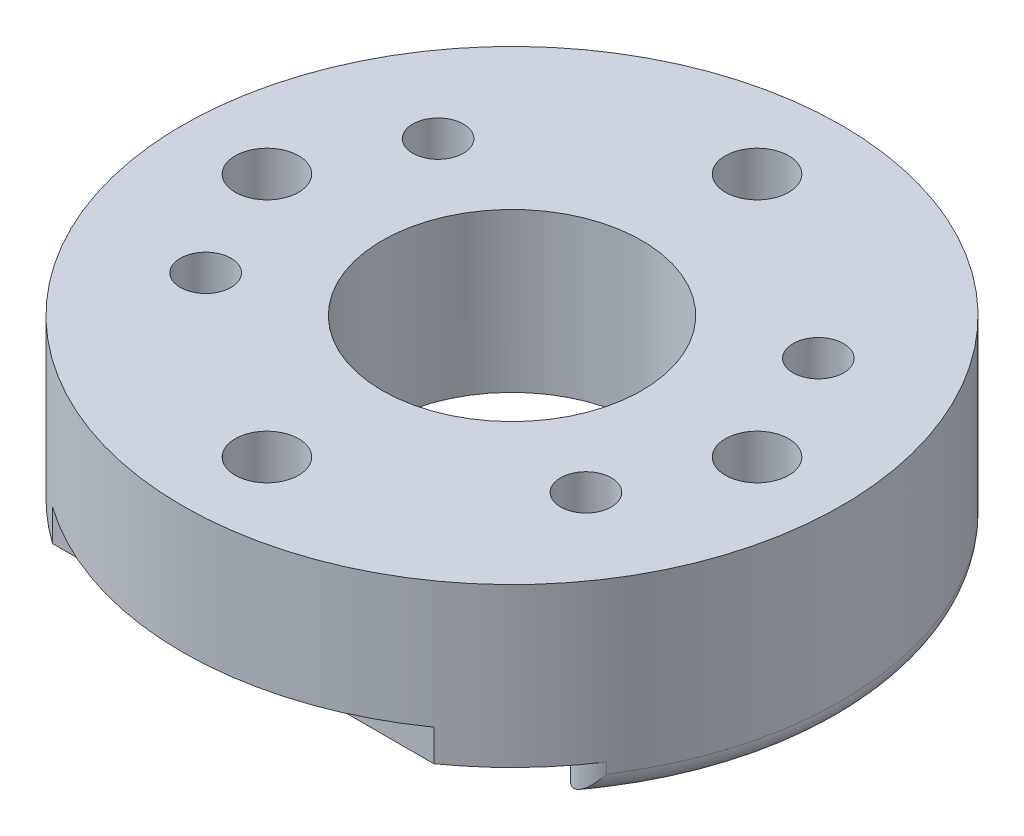
SolidWorks part; units mm, degrees
ref_plane "Front Plane" through (0, 0, 0) normal (0, 0, 1) x (1, 0, 0)
ref_plane "Top Plane" through (0, 0, 0) normal (0, 1, 0) x (1, 0, 0)
ref_plane "Right Plane" through (0, 0, 0) normal (1, 0, 0) x (0, 0, -1)
sketch "Sketch1" plane through (0, 0, 0) normal (0, 1, 0) x (1, 0, 0)
  arc A0 (16.6, 0) -> (-16.6, 0) centre (0, 0) ccw construction
  arc A1 (16.6, 0) -> (-16.6, 0) centre (0, 0) ccw
  circle A2 centre (0, 0) radius 8.5 construction
  circle A3 centre (0, 0) radius 8.5
ref_plane "Plane1" through (0, -7.5, 0) normal (0, 1, 0) x (1, 0, 0)
sketch "Sketch2" plane through (0, -7.5, 0) normal (0, 1, 0) x (1, 0, 0)
  line L4 (-11, 7.5) -> (-11, -20.5)
  line L5 (-11, -20.5) -> (11, -20.5)
  line L6 (11, -20.5) -> (11, 7.5)
  line L7 (11, 7.5) -> (-11, 7.5)
  line L8 (-11, 7.5) -> (-11, -20.5)
  line L9 (-11, -20.5) -> (11, -20.5)
  line L10 (11, -20.5) -> (11, 7.5)
  line L11 (11, 7.5) -> (-11, 7.5)
  line L16 (2.58, 2.15) -> (-2.58, 2.15)
  line L17 (2.58, -2.15) -> (2.58, 2.15)
  line L18 (-2.58, -2.15) -> (2.58, -2.15)
  line L19 (-2.58, 2.15) -> (-2.58, -2.15)
  line L20 (2.58, 2.15) -> (-2.58, 2.15)
  line L21 (2.58, -2.15) -> (2.58, 2.15)
  line L22 (-2.58, -2.15) -> (2.58, -2.15)
  line L23 (-2.58, 2.15) -> (-2.58, -2.15)
  circle A0 centre (9, -5.5) radius 1.3 construction
  circle A1 centre (9, 5.5) radius 1.3 construction
  circle A2 centre (-9, 5.5) radius 1.3 construction
  circle A3 centre (-9, -5.5) radius 1.3 construction
  circle A4 centre (9, -5.5) radius 1.3
  circle A5 centre (9, 5.5) radius 1.3
  circle A6 centre (-9, 5.5) radius 1.3
  circle A7 centre (-9, -5.5) radius 1.3
  dimension "D1" = 0
  dimension "D2" = 0
ref_plane "Plane2" through (0, -5.5, 0) normal (0, -1, 0) x (-1, 0, 0)
sketch "Sketch3" plane through (0, -5.5, 0) normal (0, -1, 0) x (-1, 0, 0)
  circle A0 centre (0, 0) radius 5.15 construction
  circle A1 centre (0, 0) radius 5.15
sketch "Sketch4" plane through (0, 0, 0) normal (0, 1, 0) x (1, 0, 0)
  circle A0 centre (0, 0) radius 15.6
  arc A1 (16.6, 0) -> (-16.6, 0) centre (0, 0) ccw construction
  circle A2 centre (0, 0) radius 5.15 construction
  circle A3 centre (0, 0) radius 5.15 construction
  circle A4 centre (0, 0) radius 6.15
  dimension "D1" = 1
  dimension "D2" = 1
extrude "Boss-Extrude1" add sketch "Sketch4" against normal up to surface (7.5 mm away) up to plane "Plane1"
sketch "Sketch5" plane through (0, -7.5, 0) normal (0, -1, 0) x (1, 0, 0)
  line L0 (11, 20.5) -> (11, -7.5) construction
  line L1 (11, -7.5) -> (-11, -7.5) construction
  line L2 (-11, -7.5) -> (-11, 20.5) construction
  line L3 (11, 11.0616) -> (11, -7.5) construction
  line L4 (11, -7.5) -> (-11, -7.5) construction
  line L5 (-11, -7.5) -> (-11, 11.0616) construction
  line L6 (11.2, 10.8591) -> (11.2, -7.7)
  line L7 (11.2, -7.7) -> (-11.2, -7.7)
  line L8 (-11.2, -7.7) -> (-11.2, 10.8591)
  line L9 (-11.2, -7.7) -> (-11.2, 20.5) construction
  line L10 (-11, -7.5) -> (-11, 20.5) construction
  line L11 (11, 20.5) -> (11, -7.5) construction
  line L12 (11.2, 20.5) -> (11.2, -7.7) construction
  arc A0 (-11.2, 10.8591) -> (11.2, 10.8591) centre (0, 0) ccw
  dimension "D1" = 0.2
extrude "Boss-Extrude2" add sketch "Sketch5" along normal blind 1.5
sketch "Sketch6" plane through (0, -7.5, 0) normal (0, -1, 0) x (1, 0, 0)
  circle A0 centre (9, -5.5) radius 1.2
  circle A1 centre (9, 5.5) radius 1.2
  circle A2 centre (-9, 5.5) radius 1.2
  circle A3 centre (-9, -5.5) radius 1.2
  dimension "D1" = 2.4
extrude "Cut-Extrude1" cut sketch "Sketch6" against normal through all
sketch "Sketch7" plane through (0, 0, 0) normal (0, 1, 0) x (1, 0, 0)
  line L0 (0, 11.6) -> (0, -11.6) construction
  line L1 (-11.6, 0) -> (11.6, 0) construction
  circle A0 centre (0, 0) radius 11.6 construction
  circle A1 centre (0, 0) radius 15.6 construction
  circle A2 centre (0, 11.6) radius 1.5
  circle A3 centre (11.6, 0) radius 1.5
  circle A4 centre (-11.6, 0) radius 1.5
  circle A5 centre (0, -11.6) radius 1.5
  dimension "D1" = 4
  dimension "D2" = 3
extrude "Cut-Extrude2" cut sketch "Sketch7" against normal through all
fillet "Fillet1" radius 1 2 edges at (-11.2, -8.25, 10.8591) (11.2, -8.25, 10.8591)
fillet "Fillet2" radius 1 1 edges at (0, -9, -15.6) tangent propagation no
sketch "Sketch8" plane through (0, -7.5, 0) normal (0, -1, 0) x (1, 0, 0)
  line L4 (-2.58, -2.15) -> (2.58, -2.15)
  line L5 (-2.58, 2.15) -> (-2.58, -2.15)
  line L6 (2.58, 2.15) -> (-2.58, 2.15)
  line L7 (2.58, -2.15) -> (2.58, 2.15)
  line L8 (-2.58, -2.15) -> (2.58, -2.15) construction
  line L9 (-2.58, 2.15) -> (-2.58, -2.15) construction
  line L10 (2.58, 2.15) -> (-2.58, 2.15) construction
  line L11 (2.58, -2.15) -> (2.58, 2.15) construction
  line L12 (-11, 20.5) -> (-11, -7.5)
  line L13 (11, 20.5) -> (-11, 20.5)
  line L14 (11, -7.5) -> (11, 20.5)
  line L15 (-11, -7.5) -> (11, -7.5)
  line L16 (-11, 20.5) -> (-11, -7.5) construction
  line L17 (11, 20.5) -> (-11, 20.5) construction
  line L18 (11, -7.5) -> (11, 20.5) construction
  line L19 (-11, -7.5) -> (11, -7.5) construction
  line L20 (2.58, 11.2678) -> (-5.0833, 11.2678)
  line L21 (-5.0833, 11.2678) -> (-5.0833, 8.1977)
  line L22 (-5.0833, 8.1977) -> (2.58, 8.1977)
  line L23 (2.58, 8.1977) -> (2.58, 11.2678)
  line L24 (2.58, 11.2678) -> (-5.0833, 11.2678)
  line L25 (-5.0833, 11.2678) -> (-5.0833, 8.1977)
  line L26 (-5.0833, 8.1977) -> (2.58, 8.1977)
  line L27 (2.58, 8.1977) -> (2.58, 11.2678)
  line L28 (10.0162, 18.7512) -> (-10.0162, 18.7512)
  line L29 (10.0162, 12.7261) -> (10.0162, 18.7512)
  line L30 (-10.0162, 12.7261) -> (10.0162, 12.7261)
  line L31 (-10.0162, 18.7512) -> (-10.0162, 12.7261)
  line L32 (10.0162, 18.7512) -> (-10.0162, 18.7512)
  line L33 (10.0162, 12.7261) -> (10.0162, 18.7512)
  line L34 (-10.0162, 12.7261) -> (10.0162, 12.7261)
  line L35 (-10.0162, 18.7512) -> (-10.0162, 12.7261)
  dimension "D1" = 0
  dimension "D2" = 0
  dimension "D3" = 0
  dimension "D4" = 0
extrude "Cut-Extrude3" cut sketch "Sketch8" against normal blind 1.5
